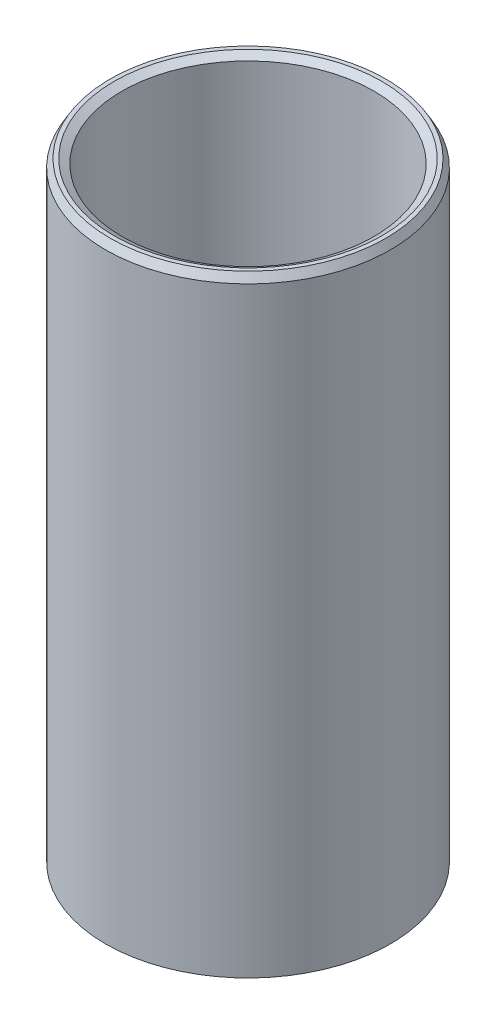
SolidWorks part; units mm, degrees
ref_plane "Front Plane" through (0, 0, 0) normal (0, 0, 1) x (1, 0, 0)
ref_plane "Top Plane" through (0, 0, 0) normal (0, 1, 0) x (1, 0, 0)
ref_plane "Right Plane" through (0, 0, 0) normal (1, 0, 0) x (0, 0, -1)
sketch "Sketch1" plane through (0, 0, 0) normal (0, 1, 0) x (1, 0, 0)
  circle A0 centre (0, 0) radius 42.5
  dimension "SLEEVE_OD" = 85
extrude "Boss-Extrude1" add sketch "Sketch1" along normal blind 183.05
sketch "Sketch2" plane through (0, 0, 0) normal (0, 1, 0) x (1, 0, 0)
  circle A0 centre (0, 0) radius 37.5986
  dimension "BORE_D" = 75.1972
extrude "Cut-Extrude1" cut sketch "Sketch2" along normal through all
chamfer "Chamfer1" distance 2.3406 angle 30 4 edges at (0, 183.05, 37.5986) (0, 0, 37.5986) (0, 0, 42.5) (0, 183.05, 42.5) first distance on face at (0, 183.05, 37.5986) first distance on face at (0, 0, 37.5986) first distance on face at (0, 183.05, 42.5)
